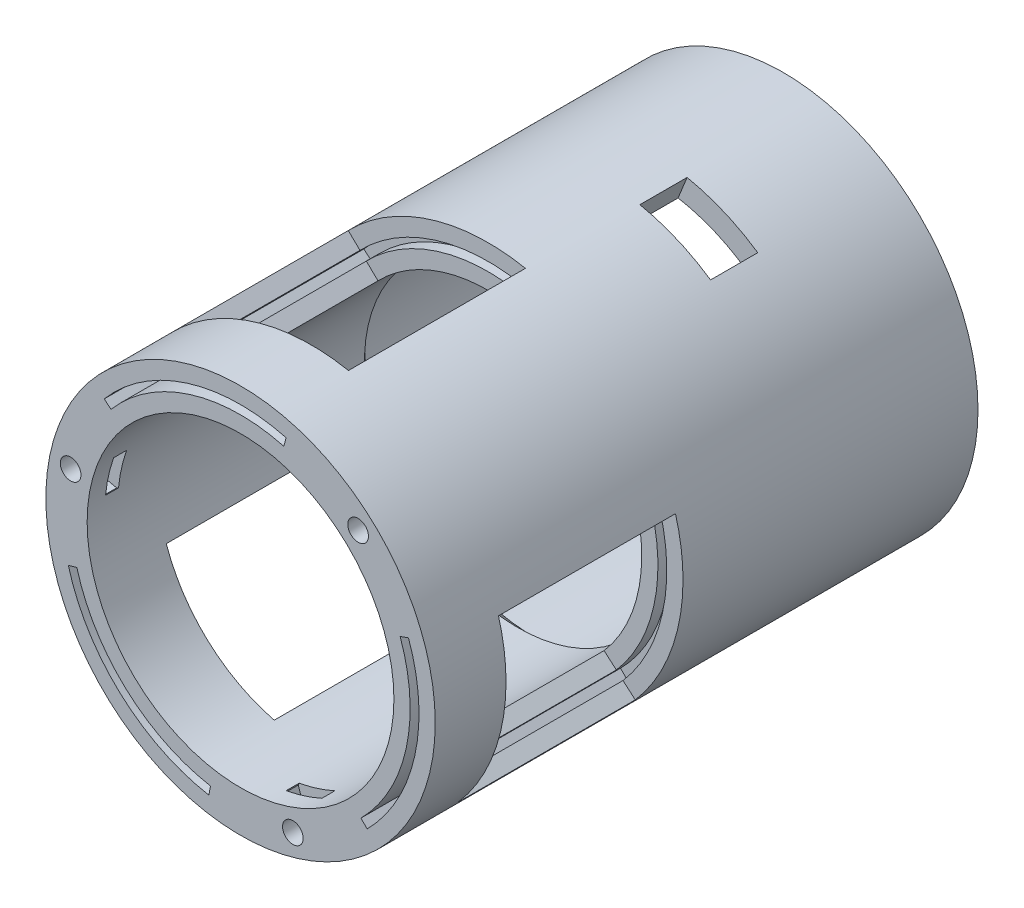
SolidWorks part; units mm, degrees
material "PEI"
ref_plane "Alzado" through (0, 0, 0) normal (0, 0, 1) x (1, 0, 0)
ref_plane "Planta" through (0, 0, 0) normal (0, 1, 0) x (1, 0, 0)
ref_plane "Vista lateral" through (0, 0, 0) normal (1, 0, 0) x (0, 0, -1)
sketch "Croquis1" plane through (0, 0, 0) normal (0, 0, 1) x (1, 0, 0)
  circle A0 centre (0, 0) radius 33
  circle A1 centre (0, 0) radius 29
  dimension "D1" = 66
  dimension "D2" = 4
extrude "Boss-Extrude1" add sketch "Croquis1" along normal blind 92
ref_axis "Eje1" through (0, 0, 92) along (0, 0, -1)
ref_plane "Plano2" through (0, 0, 0) normal (0.2756, -0.9613, 0) x (0, 0, -1)
sketch "Sketch8" plane through (0, 0, 0) normal (0, 0, -1) x (-1, 0, 0)
  arc A0 (-4, -28.7228) -> (4, -28.7228) centre (0, 0) ccw
  circle A1 centre (0, 0) radius 29 construction
  arc A2 (-4, -28.7228) -> (4, -28.7228) centre (0, -30.3008) cw
  arc A3 (-28.7228, 4) -> (-28.7228, -4) centre (0, 0) ccw
  arc A4 (-28.7228, 4) -> (-28.7228, -4) centre (-30.3008, 0) cw
  arc A5 (4, 28.7228) -> (-4, 28.7228) centre (0, 0) ccw
  arc A6 (4, 28.7228) -> (-4, 28.7228) centre (0, 30.3008) cw
  arc A7 (28.7228, -4) -> (28.7228, 4) centre (0, 0) ccw
  arc A8 (28.7228, -4) -> (28.7228, 4) centre (30.3008, 0) cw
  point P8 (0, -26.0008)
  point P20 (0, 0)
  dimension "D1" = 4.3
  dimension "D2" = 8
  dimension "D3" = 4
extrude "Boss-Extrude4" add sketch "Sketch8" against normal blind 15
sketch "Sketch9" plane through (0, 0, 0) normal (0, 0, -1) x (-1, 0, 0)
  circle A0 centre (0, -29) radius 1.75
  circle A1 centre (0, 0) radius 29 construction
  circle A2 centre (0, 0) radius 33 construction
  circle A3 centre (-29, 0) radius 1.75
  circle A4 centre (0, 29) radius 1.75
  circle A5 centre (29, 0) radius 1.75
  point P16 (0, 0)
  dimension "D1" = 4
  dimension "D2" = 3.5
  dimension "D3" = 4
extrude "Cut-Extrude3" cut sketch "Sketch9" against normal blind 14
ref_plane "Mid plane" through (0, 0, 46) normal (0, 0, 1) x (1, 0, 0)
ref_plane "Plano para USB y Switch" through (-23.3345, -23.3345, 0) normal (-0.7071, -0.7071, 0) x (0, 0, -1)
sketch "Sketch10" plane through (-23.3345, -23.3345, 0) normal (-0.7071, -0.7071, 0) x (0, 0, -1)
  line L0 (0, -33) -> (0, 33) construction
  line L1 (-10.5, 7.5) -> (-3.5, 7.5)
  line L2 (-10.5, 7.5) -> (-10.5, -7.5)
  line L3 (-10.5, -7.5) -> (-3.5, -7.5)
  line L4 (-3.5, 7.5) -> (-3.5, -7.5)
  line L5 (-10.5, 7.5) -> (-3.5, -7.5) construction
  line L6 (-10.5, -7.5) -> (-3.5, 7.5) construction
  line L8 (-42, 6.5) -> (-34, 6.5)
  line L9 (-42, 6.5) -> (-42, -6.5)
  line L10 (-42, -6.5) -> (-34, -6.5)
  line L11 (-34, 6.5) -> (-34, -6.5)
  line L12 (-42, 6.5) -> (-34, -6.5) construction
  line L13 (-42, -6.5) -> (-34, 6.5) construction
  point P0 (-7, 0)
  point P9 (-38, 0)
  dimension "D1" = 7
  dimension "D2" = 15
  dimension "D3" = 7
  dimension "D4" = 13
  dimension "D5" = 8
  dimension "D6" = 38
extrude "Corte USB y Switch" cut sketch "Sketch10" against normal blind 10
ref_plane "Plano USB PCB_C" through (12.362, 30.5971, 0) normal (0.3746, 0.9272, 0) x (0, 0, -1)
sketch "Sketch11" plane through (12.362, 30.5971, 0) normal (0.3746, 0.9272, 0) x (0, 0, -1)
  line L0 (0, -33) -> (0, 33) construction
  line L1 (-30.9, 6) -> (-22.9, 6)
  line L2 (-30.9, 6) -> (-30.9, -7)
  line L3 (-30.9, -7) -> (-22.9, -7)
  line L4 (-22.9, 6) -> (-22.9, -7)
  line L5 (-30.9, 6) -> (-22.9, -7) construction
  line L6 (-30.9, -7) -> (-22.9, 6) construction
  point P0 (-26.9, -0.5)
  dimension "D1" = 0.5
  dimension "D2" = 8
  dimension "D3" = 13
  dimension "D4" = 22.9
extrude "Cut-Extrude5" cut sketch "Sketch11" against normal blind 10
ref_plane "Plano tuercas superior" through (0, 0, 3) normal (0, 0, -1) x (-1, 0, 0)
sketch "Tuerca" plane through (0, 0, 3) normal (0, 0, -1) x (-1, 0, 0)
  line L30 (-29, -3.4064) -> (-25.5799, -3.4064)
  line L31 (-29, -3.4064) -> (-26.05, -1.7032) construction
  line L32 (-26.05, -1.7032) -> (-26.05, 1.7032) construction
  line L33 (-26.05, 1.7032) -> (-29, 3.4064) construction
  line L34 (-29, 3.4064) -> (-31.95, 1.7032)
  line L35 (-31.95, 1.7032) -> (-31.95, -1.7032)
  line L36 (-31.95, -1.7032) -> (-29, -3.4064)
  line L37 (-29, 3.4064) -> (-25.5799, 3.4064)
  circle A10 centre (-29, 0) radius 2.95 construction
  arc A12 (-25.5799, -3.4064) -> (-25.5799, 3.4064) centre (-28.2041, 0) ccw
  dimension "D4" = 5.9
extrude "Alojamiento tuerca" cut sketch "Tuerca" against normal blind 2.2 contours L30 A12 L37 L34 L35 L36 region at (27.8612, 0, 3)
pattern_circular "Alojamientos Tuercas Superior" count 4 over 360 about axis through (0, 0, 0) along (0, 0, 1) of "Alojamiento tuerca"
sketch "Sketch13" plane through (0, 0, 92) normal (0, 0, 1) x (1, 0, 0)
  circle A0 centre (0, 0) radius 29
  circle A1 centre (0, 0) radius 26
  circle A3 centre (0, 0) radius 29 construction
  circle A4 centre (0, 0) radius 33 construction
  dimension "D1" = 52
  dimension "D2" = 7
extrude "Grosor adicional" add sketch "Sketch13" against normal blind 47
sketch "Corte Revolucion" plane through (0, 0, 0) normal (0.2756, -0.9613, 0) x (0, 0, -1)
  line L0 (-80, 33) -> (-80, 25)
  line L2 (-80, 25) -> (-50, 25)
  line L4 (-50, 33) -> (-80, 33)
  line L5 (-97, 29) -> (-42, 29) construction
  line L6 (-92, 33) -> (-92, -33) construction
  line L14 (-50, 25) -> (-50, 33)
  dimension "D1" = 8
  dimension "D6" = 12
revolve "Cut-Revolve3" cut sketch "Corte Revolucion" angle 57 about axis through (0, 0, 92) along (0, 0, -1)
pattern_circular "CirPattern3" count 3 over 360 about axis through (0, 0, 0) along (0, 0, 1) of "Cut-Revolve3"
sketch "Croquis2" plane through (0, 0, 92) normal (0, 0, 1) x (1, 0, 0)
  line L0 (0, 0) -> (-23.101, 19.5296) construction
  line L1 (0, 0) -> (7.7215, 29.2479) construction
  line L2 (0, 0) -> (-21.76, 21.0134) construction
  line L3 (0, 0) -> (5.772, 29.6942) construction
  line L4 (7.7215, 29.2479) -> (7.3387, 27.7976)
  line L5 (-23.101, 19.5296) -> (-21.9555, 18.5612)
  line L6 (21.4687, -21.311) -> (20.4041, -20.2543)
  line L7 (28.4636, 10.2413) -> (27.0522, 9.7334)
  line L8 (6.2967, 32.3937) -> (4.961, 25.5223) construction
  line L9 (-23.7382, 22.9237) -> (-18.7028, 18.0611) construction
  line L10 (-29.1902, -7.9369) -> (-27.7428, -7.5433)
  line L11 (-5.3626, -29.7709) -> (-5.0967, -28.2946)
  circle A0 centre (0, 0) radius 28.75 construction
  circle A1 centre (0, 0) radius 30.25 construction
  arc A2 (28.4636, 10.2413) -> (21.4687, -21.311) centre (0, 0) cw
  circle A3 centre (0, 0) radius 29.5 construction
  arc A4 (-23.101, 19.5296) -> (7.7215, 29.2479) centre (0, 0) cw
  arc A5 (-21.9555, 18.5612) -> (7.3387, 27.7976) centre (0, 0) cw
  arc A6 (27.0522, 9.7334) -> (20.4041, -20.2543) centre (0, 0) cw
  arc A7 (-5.3626, -29.7709) -> (-29.1902, -7.9369) centre (0, 0) cw
  arc A8 (-5.0967, -28.2946) -> (-27.7428, -7.5433) centre (0, 0) cw
  circle A13 centre (0, 0) radius 33 construction
  circle A14 centre (0, 0) radius 26 construction
  point P4 (-22.5283, 19.0454)
  point P28 (0, 0)
  point P32 (0, 0)
  dimension "D1" = 1.5
  dimension "D2" = 7
  dimension "D6" = 3.5
  dimension "D3" = 2
  dimension "D4" = 2
  dimension "D5" = 3
extrude "Corte postizos" cut sketch "Croquis2" against normal offset from surface (44 mm away) 2 up to face at (-8.3333, 26.4299, 50) offset beyond the face yes
chamfer "Chamfer3" distance 3 angle 45 1 edges at (29, 0, 45)
sketch "Sketch14" plane through (0, 0, 92) normal (0, 0, 1) x (1, 0, 0)
  line L0 (7.3387, 27.7976) -> (0, 0) construction
  line L1 (0, 0) -> (27.0522, 9.7334) construction
  line L2 (0, 0) -> (19.9299, 21.7497) construction
  line L3 (28.4636, 10.2413) -> (27.0522, 9.7334) construction
  line L4 (7.7215, 29.2479) -> (7.3387, 27.7976) construction
  line L5 (0, 0) -> (8.8708, -28.1347) construction
  line L6 (0, 0) -> (-28.8007, 6.385) construction
  arc A0 (27.7579, 9.9874) -> (7.5301, 28.5228) centre (0, 0) ccw construction
  circle A1 centre (19.9299, 21.7497) radius 1.75
  circle A2 centre (8.8708, -28.1347) radius 1.75
  arc A3 (-5.2297, -29.0328) -> (20.9364, -20.7826) centre (0, 0) ccw construction
  circle A4 centre (-28.8007, 6.385) radius 1.75
  arc A5 (-22.5283, 19.0454) -> (-28.4665, -7.7401) centre (0, 0) ccw construction
  point P21 (15.6241, 4.4801)
  point P25 (0, 0)
  dimension "D3" = 3.5
  dimension "D1" = 55.422
  dimension "D2" = 27.711
  dimension "D4" = 3
extrude "Cut-Extrude6" cut sketch "Sketch14" against normal blind 17
ref_plane "Plano tuercas inferior" through (0, 0, 89) normal (0, 0, 1) x (1, 0, 0)
sketch "Sketch15" plane through (0, 0, 89) normal (0, 0, 1) x (1, 0, 0)
  line L0 (17.4155, 24.0477) -> (15.1082, 21.5231)
  line L1 (17.4155, 24.0477) -> (16.6825, 20.7211) construction
  line L2 (16.6825, 20.7211) -> (19.197, 18.4231) construction
  line L3 (19.197, 18.4231) -> (22.4444, 19.4517) construction
  line L4 (22.4444, 19.4517) -> (23.1773, 22.7783)
  line L5 (23.1773, 22.7783) -> (20.6628, 25.0763)
  line L6 (20.6628, 25.0763) -> (17.4155, 24.0477)
  line L7 (22.4444, 19.4517) -> (20.1371, 16.9271)
  line L8 (12.1182, -27.1061) -> (11.0855, -23.8456)
  line L9 (5.6235, -29.1632) -> (8.1379, -31.4612)
  line L10 (8.1379, -31.4612) -> (11.3853, -30.4327)
  line L11 (11.3853, -30.4327) -> (12.1182, -27.1061)
  line L12 (5.6235, -29.1632) -> (4.5907, -25.9027)
  line L13 (12.1182, -27.1061) -> (9.6037, -24.8081) construction
  line L14 (9.6037, -24.8081) -> (6.3564, -25.8366) construction
  line L15 (6.3564, -25.8366) -> (5.6235, -29.1632) construction
  line L16 (-29.5336, 3.0584) -> (-26.1936, 2.3225)
  line L17 (-28.0678, 9.7116) -> (-31.3152, 8.683)
  line L18 (-31.3152, 8.683) -> (-32.0481, 5.3564)
  line L19 (-32.0481, 5.3564) -> (-29.5336, 3.0584)
  line L20 (-28.0678, 9.7116) -> (-24.7278, 8.9757)
  line L21 (-29.5336, 3.0584) -> (-26.2863, 4.087) construction
  line L22 (-26.2863, 4.087) -> (-25.5534, 7.4135) construction
  line L23 (-25.5534, 7.4135) -> (-28.0678, 9.7116) construction
  circle A0 centre (19.9299, 21.7497) radius 2.95 construction
  arc A1 (15.1082, 21.5231) -> (20.1371, 16.9271) centre (19.393, 21.1622) ccw
  arc A2 (11.0855, -23.8456) -> (4.5907, -25.9027) centre (8.6305, -27.3759) ccw
  circle A3 centre (8.8708, -28.1347) radius 2.95 construction
  arc A5 (-26.1936, 2.3225) -> (-24.7278, 8.9757) centre (-28.0235, 6.2137) ccw
  circle A6 centre (-28.8007, 6.385) radius 2.95 construction
  point P38 (0, 0)
  dimension "D1" = 5.9
  dimension "D2" = 240
  dimension "D3" = 240
  dimension "D4" = 210
  dimension "D5" = 240
  dimension "D6" = 3.4201
  dimension "D7" = 3
extrude "Tuercas inferior" cut sketch "Sketch15" against normal blind 2.2
equation "\"D6@Croquis2\"=\"D2@Croquis2\"/2"
equation "\"D2@Sketch14\"=\"D1@Sketch14\"/2"
equation "\"D3@Sketch15\"=\"D2@Sketch15\""
equation "\"D5@Sketch15\"=\"D3@Sketch15\""
